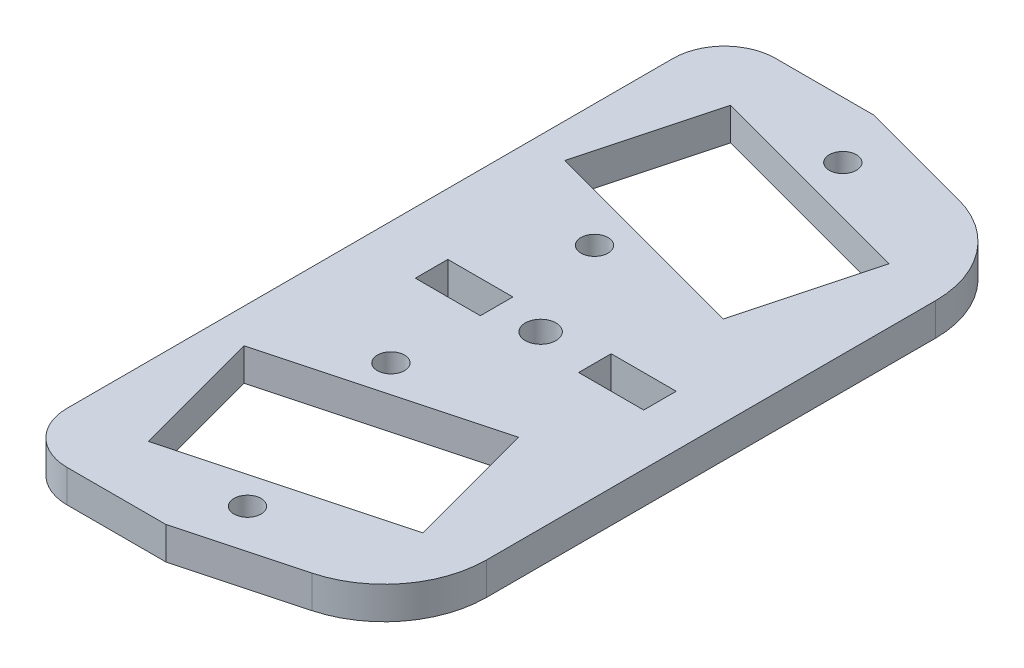
SolidWorks part; units mm, degrees
ref_plane "Front Plane" through (0, 0, 0) normal (0, 0, 1) x (1, 0, 0)
ref_plane "Top Plane" through (0, 0, 0) normal (0, 1, 0) x (1, 0, 0)
ref_plane "Right Plane" through (0, 0, 0) normal (1, 0, 0) x (0, 0, -1)
sketch "Sketch1" plane through (0, 0, 0) normal (0, 1, 0) x (1, 0, 0)
  line L0 (240.608, 10.8557) -> (261.7408, 5.1932)
  line L1 (242.2575, 29.7812) -> (251.8972, 29.7812)
  line L2 (237.2575, 24.7812) -> (237.2575, -34.3947)
  line L4 (270.5575, 17.1079) -> (270.5575, -26.7215)
  line L5 (240.608, 10.8557) -> (244.0251, 23.6083)
  line L6 (261.7408, 5.1932) -> (265.1579, 17.9458)
  line L7 (244.0251, 23.6083) -> (265.1579, 17.9458)
  line L8 (253.0712, 24.5996) -> (255.6305, 23.9137) construction
  line L9 (252.1737, 16.1327) -> (251.4878, 13.5732) construction
  line L10 (242.3166, 17.232) -> (263.4494, 11.5695) construction
  line L11 (237.2575, -4.8068) -> (270.5575, -4.8068) construction
  line L12 (242.3166, -26.8456) -> (263.4494, -21.1831) construction
  line L13 (252.1737, -25.7463) -> (251.4878, -23.1868) construction
  line L14 (253.0712, -34.2132) -> (255.6305, -33.5273) construction
  line L15 (261.7408, -14.8068) -> (265.1579, -27.5593)
  line L16 (240.608, -20.4693) -> (261.7408, -14.8068)
  line L17 (244.0251, -33.2219) -> (240.608, -20.4693)
  line L18 (265.1579, -27.5593) -> (244.0251, -33.2219)
  line L19 (251.8972, -39.3947) -> (263.1457, -36.3807)
  line L20 (243.2575, -6.3943) -> (249.6075, -6.3943)
  line L21 (243.2575, -6.3943) -> (243.2575, -3.2193)
  line L22 (243.2575, -3.2193) -> (249.6075, -3.2193)
  line L23 (249.6075, -6.3943) -> (249.6075, -3.2193)
  line L24 (243.2575, -6.3943) -> (249.6075, -3.2193) construction
  line L25 (243.2575, -3.2193) -> (249.6075, -6.3943) construction
  line L26 (259.2075, -6.3943) -> (265.5575, -6.3943)
  line L27 (259.2075, -6.3943) -> (259.2075, -3.2193)
  line L28 (259.2075, -3.2193) -> (265.5575, -3.2193)
  line L29 (265.5575, -6.3943) -> (265.5575, -3.2193)
  line L30 (259.2075, -6.3943) -> (265.5575, -3.2193) construction
  line L31 (259.2075, -3.2193) -> (265.5575, -6.3943) construction
  line L32 (251.8972, 29.7812) -> (263.1457, 26.7672)
  line L33 (242.2575, -39.3947) -> (251.8972, -39.3947)
  circle A0 centre (254.3509, 24.2567) radius 1.3248
  circle A1 centre (249.2262, 5.1313) radius 1.3248
  circle A2 centre (249.2262, -14.7449) radius 1.3248
  circle A3 centre (254.3509, -33.8702) radius 1.3248
  circle A4 centre (253.9075, -4.8068) radius 1.5
  arc A5 (237.2575, -34.3947) -> (242.2575, -39.3947) centre (242.2575, -34.3947) ccw
  arc A6 (270.5575, -26.7215) -> (263.1457, -36.3807) centre (260.5575, -26.7215) cw
  arc A7 (270.5575, 17.1079) -> (263.1457, 26.7672) centre (260.5575, 17.1079) ccw
  arc A8 (242.2575, 29.7812) -> (237.2575, 24.7812) centre (242.2575, 24.7812) ccw
  point P26 (246.4325, -4.8068)
  point P31 (262.3825, -4.8068)
  point P43 (270.5575, -34.3947)
  point P44 (270.5575, 29.7812)
  point P47 (237.2575, 29.7812)
  point P51 (270.5575, 24.7812)
  dimension "D10" = 3
  dimension "D11" = 5
  dimension "D12" = 19.8
  dimension "D9" = 10
  dimension "D1" = 10
  dimension "D2" = 3.175
  dimension "D3" = 3.175
  dimension "D4" = 6.35
  dimension "D5" = 6.35
  dimension "D6" = 5
  dimension "D7" = 9.6
  dimension "D8" = 6
  dimension "D13" = 8
extrude "Boss-Extrude1" add sketch "Sketch1" along normal blind 3.175
